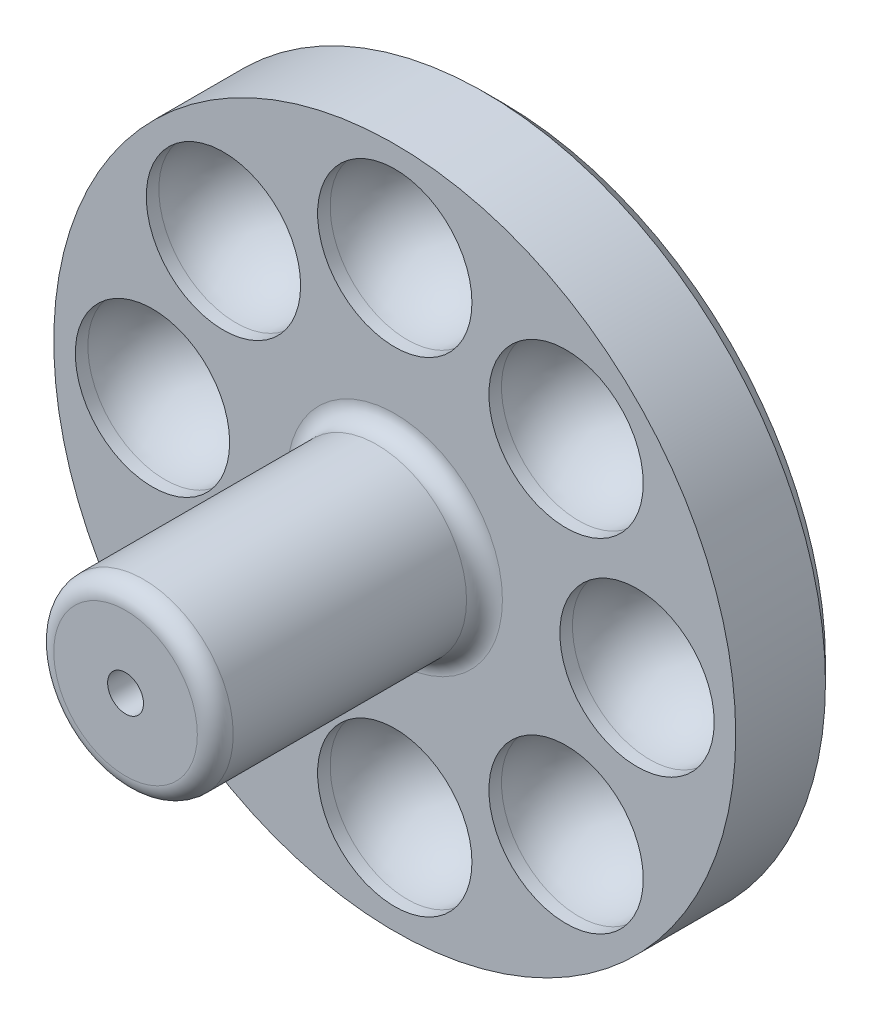
SolidWorks part; units mm, degrees
ref_plane "Front Plane" through (0, 0, 0) normal (0, 0, 1) x (1, 0, 0)
ref_plane "Top Plane" through (0, 0, 0) normal (0, 1, 0) x (1, 0, 0)
ref_plane "Right Plane" through (0, 0, 0) normal (1, 0, 0) x (0, 0, -1)
sketch "Sketch1" plane through (0, 0, 0) normal (0, 0, 1) x (1, 0, 0)
  circle A0 centre (0, 0) radius 19
  circle A1 centre (0, 0) radius 1
  dimension "D1" = 2
  dimension "D2" = 38
extrude "Boss-Extrude1" add sketch "Sketch1" along normal blind 6
sketch "Sketch2" plane through (0, 0, 6) normal (0, 0, 1) x (1, 0, 0)
  circle A0 centre (0, 13.5) radius 4.3
  circle A1 centre (9.5459, 9.5459) radius 4.3
  circle A2 centre (13.5, 0) radius 4.3
  circle A3 centre (9.5459, -9.5459) radius 4.3
  circle A4 centre (0, -13.5) radius 4.3
  circle A5 centre (-9.5459, -9.5459) radius 4.3
  circle A6 centre (-13.5, 0) radius 4.3
  circle A7 centre (-9.5459, 9.5459) radius 4.3
  point P19 (0, 0)
  dimension "D2" = 8.6
  dimension "D1" = 13.5
  dimension "D3" = 8
extrude "Cut-Extrude1" cut sketch "Sketch2" against normal offset from surface (5 mm away) 1 up to face at (19, 0, 0)
fillet "Fillet1" radius 4.3 8 edges at (-5.2459, -9.5459, 1) (4.3, -13.5, 1) (13.8459, -9.5459, 1) (17.8, 0, 1) (13.8459, 9.5459, 1) (4.3, 13.5, 1) (-9.2, 0, 1) (-5.2459, 9.5459, 1)
sketch "Sketch3" plane through (0, 0, 6) normal (0, 0, 1) x (1, 0, 0)
  circle A0 centre (0, 0) radius 5
  circle A1 centre (0, 0) radius 1
  dimension "D1" = 10
extrude "Boss-Extrude2" add sketch "Sketch3" along normal blind 15
fillet "Fillet2" radius 1 2 edges at (5, 0, 21) (5, 0, 6)
chamfer "Chamfer1" distance 1 angle 45 1 edges at (19, 0, 0)
